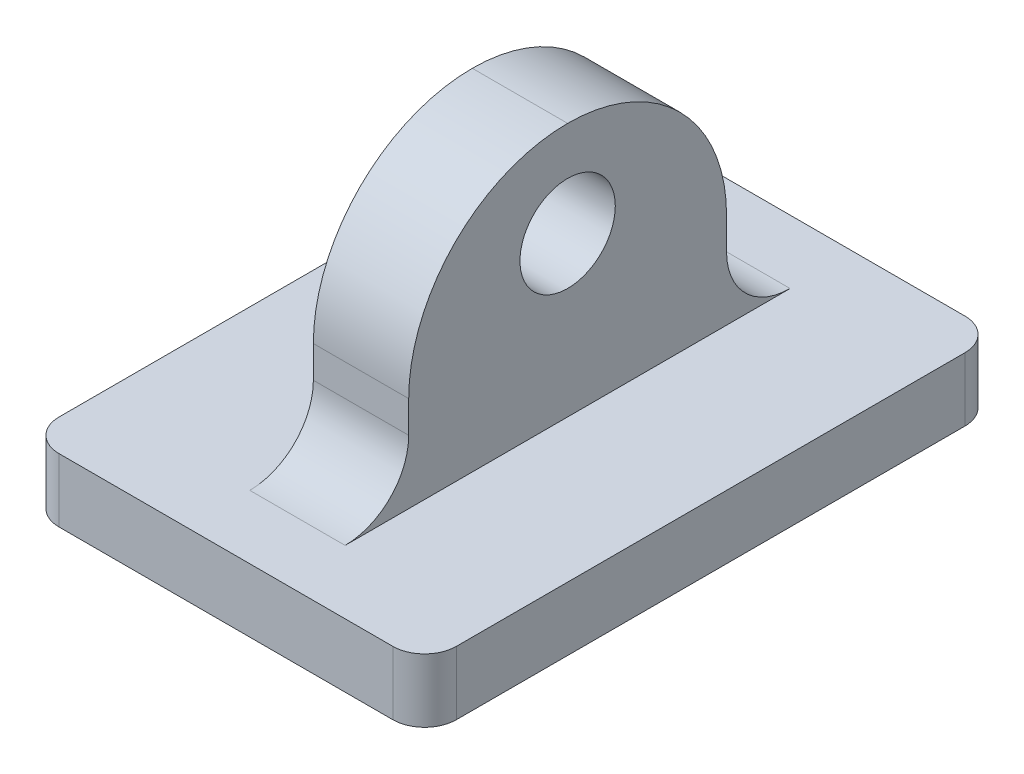
SolidWorks part; units mm, degrees
ref_plane "Front Plane" through (0, 0, 0) normal (0, 0, 1) x (1, 0, 0)
ref_plane "Top Plane" through (0, 0, 0) normal (0, 1, 0) x (1, 0, 0)
ref_plane "Right Plane" through (0, 0, 0) normal (1, 0, 0) x (0, 0, -1)
sketch "Sketch1" plane through (0, 0, 0) normal (0, 1, 0) x (1, 0, 0)
  line L1 (-35, -75) -> (35, -75)
  line L2 (-35, -75) -> (-35, 75)
  line L3 (-35, 75) -> (35, 75)
  line L4 (35, -75) -> (35, 75)
  line L5 (-35, -75) -> (35, 75) construction
  line L6 (-35, 75) -> (35, -75) construction
  point P0 (0, 0)
  dimension "D1" = 150
  dimension "D2" = 70
extrude "Boss-Extrude1" add sketch "Sketch1" along normal blind 5
sketch "Sketch2" plane through (0, 5, 0) normal (0, 1, 0) x (1, 0, 0)
  line L0 (35, 75) -> (-35, 75) construction
  line L1 (-5, 55) -> (-2, 55)
  line L2 (-5, 55) -> (-5, 70)
  line L3 (-5, 70) -> (-2, 70)
  line L4 (-2, 55) -> (-2, 70)
  line L5 (-5, 55) -> (-2, 70) construction
  line L6 (-5, 70) -> (-2, 55) construction
  line L7 (2, 55) -> (5, 55)
  line L8 (2, 55) -> (2, 70)
  line L9 (2, 70) -> (5, 70)
  line L10 (5, 55) -> (5, 70)
  line L11 (2, 55) -> (5, 70) construction
  line L12 (2, 70) -> (5, 55) construction
  line L13 (0, 0) -> (0, 91.7646) construction
  line L15 (-8, 51.5) -> (8, 51.5)
  line L16 (-8, 51.5) -> (-8, 73.5)
  line L17 (-8, 73.5) -> (8, 73.5)
  line L18 (8, 51.5) -> (8, 73.5)
  line L19 (-8, 51.5) -> (8, 73.5) construction
  line L20 (-8, 73.5) -> (8, 51.5) construction
  point P0 (-3.5, 62.5)
  point P5 (3.5, 62.5)
  point P15 (0, 62.5)
  dimension "D1" = 15
  dimension "D2" = 15
  dimension "D3" = 10
  dimension "D4" = 3
  dimension "D5" = 3
  dimension "D6" = 5
  dimension "D7" = 5
  dimension "D8" = 2
  dimension "D9" = 22
  dimension "D10" = 16
  dimension "D11" = 3.5
extrude "Boss-Extrude3" add sketch "Sketch2" along normal blind 20 contours L7 L10 L9 L8 | L2 L3 L4 L1 region at (3.5, 5, -62.5)
extrude "Boss-Extrude4" add sketch "Sketch2<5>" along normal blind 5
sketch "Sketch2<5>" plane through (0, 5, 0) normal (0, 1, 0) x (1, 0, 0) same geometry as "Sketch2"
chamfer "Chamfer1" distance 3 angle 45 2 edges at (0, 10, -73.5) (0, 10, -51.5)
sketch "Sketch3" plane through (5, 0, 0) normal (1, 0, 0) x (0, 0, -1)
  line L0 (55, 25) -> (70, 25) construction
  line L1 (70, 25) -> (70, 10) construction
  circle A0 centre (62.5, 23.2) radius 3
  dimension "D1" = 6
  dimension "D2" = 1.8
  dimension "D3" = 7.5
extrude "Cut-Extrude1" cut sketch "Sketch3" against normal through all
chamfer "Chamfer3" distance 1 angle 45 4 edges at (3.5, 25, -60.1) (-3.5, 25, -60.1) (-3.5, 25, -64.9) (3.5, 25, -64.9) first distance on face at (3.5, 25, -57.55) first distance on face at (-3.5, 25, -57.55) first distance on face at (-3.5, 25, -67.45) first distance on face at (3.5, 25, -67.45)
chamfer "Chamfer4" distance 1 angle 45 4 edges at (3.5, 25, -55) (-3.5, 25, -55) (-3.5, 25, -70) (3.5, 25, -70)
chamfer "Chamfer5" distance 3 angle 45 2 edges at (-8, 5, -62.5) (8, 5, -62.5)
chamfer "Chamfer6" distance 3 angle 45 2 edges at (-5, 10, -62.5) (5, 10, -62.5)
chamfer "Chamfer7" distance 20 angle 45 2 edges at (-35, 2.5, 75) (35, 2.5, 75)
chamfer "Chamfer8" distance 10 angle 45 2 edges at (-35, 2.5, -75) (35, 2.5, -75)
sketch "Sketch4" plane through (0, 5, 0) normal (0, 1, 0) x (1, 0, 0)
  line L0 (-15, -75) -> (15, -75) construction
  line L5 (35, -55) -> (35, 65) construction
  line L7 (-1.5, -75) -> (1.5, -75)
  line L8 (-1.5, -75) -> (-1.5, -65)
  line L9 (-1.5, -65) -> (1.5, -65)
  line L10 (1.5, -75) -> (1.5, -65)
  line L11 (-1.5, -75) -> (1.5, -65) construction
  line L12 (-1.5, -65) -> (1.5, -75) construction
  point P5 (0, -70)
  dimension "D1" = 3
  dimension "D2" = 10
  dimension "D3" = 0
  dimension "D4" = 33.5
extrude "Boss-Extrude5" add sketch "Sketch4" along normal blind 10
sketch "Sketch6" plane through (1.5, 0, 0) normal (1, 0, 0) x (0, 0, -1)
  line L0 (-75, 15) -> (-65, 15) construction
  line L1 (-65, 15) -> (-65, 5) construction
  circle A0 centre (-70, 12) radius 1.5
  dimension "D1" = 3
  dimension "D2" = 3
  dimension "D3" = 5
extrude "Cut-Extrude2" cut sketch "Sketch6" against normal through all
fillet "Fillet1" radius 5 2 edges at (0, 15, 75) (0, 15, 65)
chamfer "Chamfer10" distance 1 angle 45 8 edges at (0, 0, 75) (-25, 0, 65) (-35, 0, -5) (-30, 0, -70) (0, 0, -75) (30, 0, -70) (35, 0, -5) (25, 0, 65)
sketch "Sketch7" plane through (-35, 0, 0) normal (-1, 0, 0) x (0, 0, 1)
  line L0 (-65, 5) -> (55, 5) construction
  line L1 (-104.7665, 57.5685) -> (-5.9777, 57.5685)
  line L2 (-104.7665, 57.5685) -> (-104.7665, -7.0847)
  line L3 (-104.7665, -7.0847) -> (-5.9777, -7.0847)
  line L4 (-5.9777, 57.5685) -> (-5.9777, 5)
  line L5 (-5.9777, 5) -> (81.485, 5)
  line L6 (-5.9777, -7.0847) -> (-5.9777, -30.2089)
  line L7 (-5.9777, -30.2089) -> (81.485, -30.2089)
  line L8 (81.485, 5) -> (81.485, -30.2089)
extrude "Cut-Extrude3" cut sketch "Sketch7" against normal blind 87
sketch "Sketch8" plane through (-1.5, 0, 0) normal (-1, 0, 0) x (0, 0, 1)
  line L0 (65, 5) -> (75, 5) construction
  line L1 (61, 7) -> (79, 7)
  line L2 (61, 7) -> (61, 5)
  line L3 (61, 5) -> (79, 5)
  line L4 (79, 7) -> (79, 5)
  line L5 (75, 5) -> (65, 5) construction
  point P6 (70, 5)
  point P7 (70, 7)
  point P10 (70, 5)
  dimension "D1" = 18
  dimension "D2" = 2
extrude "Boss-Extrude6" add sketch "Sketch8" along normal blind 5 and the other way blind 7.5
fillet "Fillet2" radius 2 2 edges at (0, 7, 75) (0, 7, 65)
fillet "Fillet3" radius 1 4 edges at (-6.5, 6, 61) (6, 6, 61) (6, 6, 79) (-6.5, 6, 79)
